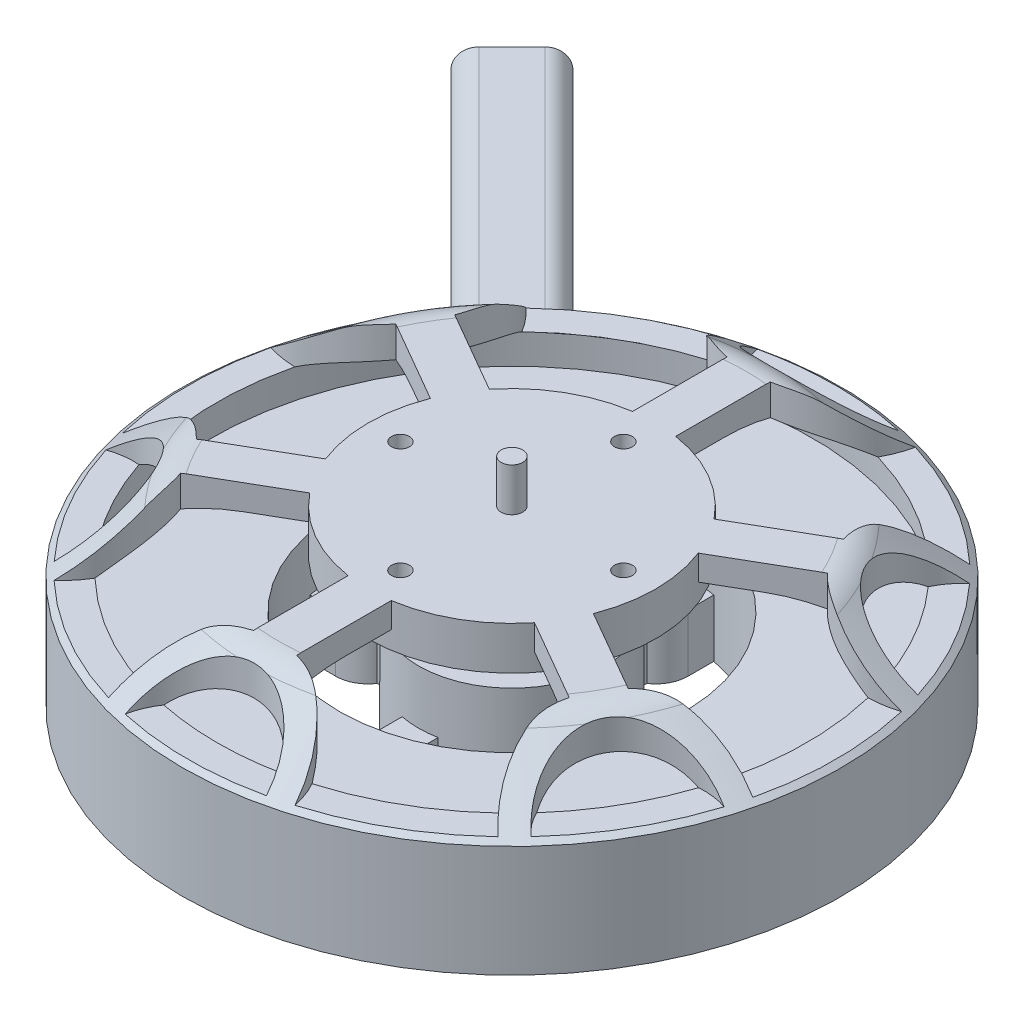
SolidWorks part; units mm, degrees
ref_plane "Front Plane" through (0, 0, 0) normal (0, 0, 1) x (1, 0, 0)
ref_plane "Top Plane" through (0, 0, 0) normal (0, 1, 0) x (1, 0, 0)
ref_plane "Right Plane" through (0, 0, 0) normal (1, 0, 0) x (0, 0, -1)
ref_axis "Axis1" through (0, 40.089, 0) along (0, -1, 0)
sketch "Sketch1" plane through (0, 0, 0) normal (0, 0, 1) x (1, 0, 0)
  line L0 (0, 0) -> (9.65, 0)
  line L1 (9.65, 0) -> (9.65, 3.93)
  line L2 (9.65, 3.93) -> (27.5, 3.93)
  line L3 (27.5, 3.93) -> (45.83, 8.08)
  line L4 (45.83, 8.08) -> (45.83, 23.58)
  line L5 (45.83, 23.58) -> (36.1322, 30.9557)
  line L6 (32.5, 32.18) -> (1.5, 32.18)
  line L7 (1.5, 32.18) -> (1.5, 38.18)
  line L8 (1.5, 38.18) -> (0, 38.18)
  line L9 (0, 38.18) -> (0, 0) construction
  line L10 (0, 0) -> (0, 38.18)
  arc A0 (36.1322, 30.9557) -> (32.5, 32.18) centre (32.5, 26.18) ccw
  dimension "D10" = 6
  dimension "D1" = 3
  dimension "D2" = 6
  dimension "D3" = 28.25
  dimension "D4" = 3.93
  dimension "D5" = 19.3
  dimension "D6" = 4.15
  dimension "D7" = 91.66
  dimension "D8" = 55
  dimension "D9" = 65
  dimension "D11" = 15.5
revolve "Revolve1" add sketch "Sketch1" angle 360 about L9
sketch "Sketch2" plane through (0, 3.93, 0) normal (0, -1, 0) x (1, 0, 0)
  line L0 (0, 0) -> (0, 27.5) construction
  line L1 (2.5, 12.7574) -> (2.5, 16.2583)
  line L2 (4.5, 20) -> (4.5, 23.5744)
  line L3 (0, 0) -> (16.9706, 16.9706) construction
  line L4 (20, 4.5) -> (23.5744, 4.5)
  line L5 (12.7574, 2.5) -> (16.2583, 2.5)
  line L6 (20, -4.5) -> (23.5744, -4.5)
  line L7 (4.5, -20) -> (4.5, -23.5744)
  line L8 (2.5, -12.7574) -> (2.5, -16.2583)
  line L9 (12.7574, -2.5) -> (16.2583, -2.5)
  line L10 (-4.5, -20) -> (-4.5, -23.5744)
  line L11 (-20, -4.5) -> (-23.5744, -4.5)
  line L12 (-12.7574, -2.5) -> (-16.2583, -2.5)
  line L13 (-2.5, -12.7574) -> (-2.5, -16.2583)
  line L14 (-20, 4.5) -> (-23.5744, 4.5)
  line L15 (-4.5, 20) -> (-4.5, 23.5744)
  line L16 (-2.5, 12.7574) -> (-2.5, 16.2583)
  line L17 (-12.7574, 2.5) -> (-16.2583, 2.5)
  arc A0 (4.5, 23.5744) -> (23.5744, 4.5) centre (0, 0) cw
  arc A1 (4.5, 20) -> (2.5, 16.2583) centre (0, 20) cw
  arc A2 (2.5, 12.7574) -> (12.7574, 2.5) centre (0, 0) cw
  circle A3 centre (0, 0) radius 27.5 construction
  arc A4 (20, 4.5) -> (16.2583, 2.5) centre (20, 0) ccw
  arc A5 (20, -4.5) -> (16.2583, -2.5) centre (20, 0) cw
  arc A6 (23.5744, -4.5) -> (4.5, -23.5744) centre (0, 0) cw
  arc A7 (4.5, -20) -> (2.5, -16.2583) centre (0, -20) ccw
  arc A8 (12.7574, -2.5) -> (2.5, -12.7574) centre (0, 0) cw
  arc A9 (-4.5, -20) -> (-2.5, -16.2583) centre (0, -20) cw
  arc A10 (-4.5, -23.5744) -> (-23.5744, -4.5) centre (0, 0) cw
  arc A11 (-20, -4.5) -> (-16.2583, -2.5) centre (-20, 0) ccw
  arc A12 (-2.5, -12.7574) -> (-12.7574, -2.5) centre (0, 0) cw
  arc A13 (-20, 4.5) -> (-16.2583, 2.5) centre (-20, 0) cw
  arc A14 (-23.5744, 4.5) -> (-4.5, 23.5744) centre (0, 0) cw
  arc A15 (-4.5, 20) -> (-2.5, 16.2583) centre (0, 20) ccw
  arc A16 (-12.7574, 2.5) -> (-2.5, 12.7574) centre (0, 0) cw
  point P4 (0, 20)
  point P51 (0, 0)
  dimension "D2" = 13
  dimension "D5" = 24
  dimension "D1" = 20
  dimension "D3" = 5
  dimension "D4" = 9
  dimension "D6" = 45
  dimension "D7" = 4
hole_wizard "M4x0.7 Tapped Hole1" positions "3DSketch1" profile "Sketch4" tap size "M4x0.7" standard "ANSI Metric"
sketch3d "3DSketch1"
  point P0 (-20, 3.93, 0)
  point P3 (0, 3.93, 20)
  point P6 (20, 3.93, 0)
  point P9 (0, 3.93, -20)
sketch "Sketch4" plane through (-20, 3.93, 0) normal (1, 0, 0) x (0, 0, -1)
  line L0 (0, 0) -> (0, 8.9914)
  line L1 (0, 8.9914) -> (1.65, 8)
  line L2 (1.65, 8) -> (1.65, 0)
  line L5 (1.65, 0) -> (0, 0)
  line L10 (0, 8.9914) -> (-1.65, 8) construction
  line L11 (0, -6.35) -> (0, 107.95) construction
  dimension "Tap Drill Dia." = 3.3
  dimension "Tap Drill Depth" = 8
  dimension "Drill Angle" = 118
cosmetic thread "Hole Thread1" parameters "D1"=7.874, "D2"=4
cosmetic thread "Hole Thread2" parameters "D1"=7.874, "D2"=4
cosmetic thread "Hole Thread3" parameters "D1"=7.874, "D2"=4
cosmetic thread "Hole Thread4" parameters "D1"=7.874, "D2"=4
extrude "Cut-Extrude1" cut sketch "Sketch2" against normal blind 8
sketch "Sketch5" plane through (0, 0, 0) normal (0, 0, 1) x (1, 0, 0)
  line L0 (24, 19.43) -> (41.83, 19.43)
  line L1 (-27.5, 3.93) -> (27.5, 3.93) construction
  line L2 (41.83, 19.43) -> (41.83, 23.58)
  line L3 (45.83, 8.08) -> (45.83, 23.58) construction
  line L4 (10, 19.43) -> (13, 19.43)
  line L5 (13, 19.43) -> (13, 11.93)
  line L6 (13, 11.93) -> (24, 11.93)
  line L7 (24, 11.93) -> (24, 19.43)
  line L8 (0, 40.089) -> (0, -1.909) construction
  line L9 (4.5, 11.93) -> (23.5744, 11.93) construction
  line L10 (45.83, 23.58) -> (-45.83, 23.58) construction
  line L11 (20, 28.68) -> (26.6996, 28.68)
  line L12 (32.5, 32.18) -> (-32.5, 32.18) construction
  line L13 (41.83, 23.58) -> (45.83, 20.5378) construction
  line L14 (45.83, 23.58) -> (36.1322, 30.9557) construction
  line L15 (20, 28.68) -> (20, 26.18)
  line L16 (20, 26.18) -> (10, 26.18)
  line L17 (10, 26.18) -> (10, 19.43)
  arc A0 (26.6996, 28.68) -> (41.83, 23.58) centre (26.6996, 3.6861) cw
  dimension "D1" = 15.5
  dimension "D2" = 4
  dimension "D3" = 13
  dimension "D4" = 24
  dimension "D5" = 3.5
  dimension "D6" = 20
  dimension "D7" = 6
  dimension "D8" = 10
revolve "Cut-Revolve3" cut sketch "Sketch5" angle 360 about axis through (0, 40.089, 0) along (0, -1, 0)
sketch "Sketch6" plane through (0, 0, 0) normal (0, 1, 0) x (1, 0, 0)
  line L0 (-3, 19.7737) -> (-3, 32.9241)
  line L1 (3, 19.7737) -> (3, 32.9241)
  line L2 (-3, 19.7737) -> (3, 19.7737) construction
  line L3 (0, 45.83) -> (0, 35.83) construction
  line L4 (15.6245, 12.4849) -> (27.0131, 19.0601)
  line L5 (18.6245, 7.2888) -> (30.0131, 13.864)
  line L6 (15.6245, 12.4849) -> (18.6245, 7.2888) construction
  line L7 (39.6899, 22.915) -> (31.0297, 17.915) construction
  line L8 (18.6245, -7.2888) -> (30.0131, -13.864)
  line L9 (15.6245, -12.4849) -> (27.0131, -19.0601)
  line L10 (18.6245, -7.2888) -> (15.6245, -12.4849) construction
  line L11 (39.6899, -22.915) -> (31.0297, -17.915) construction
  line L12 (3, -19.7737) -> (3, -32.9241)
  line L13 (-3, -19.7737) -> (-3, -32.9241)
  line L14 (3, -19.7737) -> (-3, -19.7737) construction
  line L15 (0, -45.83) -> (0, -35.83) construction
  line L16 (-15.6245, -12.4849) -> (-27.0131, -19.0601)
  line L17 (-18.6245, -7.2888) -> (-30.0131, -13.864)
  line L18 (-15.6245, -12.4849) -> (-18.6245, -7.2888) construction
  line L19 (-39.6899, -22.915) -> (-31.0297, -17.915) construction
  line L20 (-18.6245, 7.2888) -> (-30.0131, 13.864)
  line L21 (-15.6245, 12.4849) -> (-27.0131, 19.0601)
  line L22 (-18.6245, 7.2888) -> (-15.6245, 12.4849) construction
  line L23 (-39.6899, 22.915) -> (-31.0297, 17.915) construction
  line L24 (0, 15.5) -> (15.5, 0) construction
  line L25 (15.5, 0) -> (0, -15.5) construction
  line L26 (0, -15.5) -> (-15.5, 0) construction
  line L27 (-15.5, 0) -> (0, 15.5) construction
  arc A1 (-9.9403, 44.739) -> (9.9403, 44.739) centre (0, 45.83) ccw
  circle A2 centre (0, 0) radius 45.83 construction
  arc A3 (-13.1108, 43.9146) -> (-3, 32.9241) centre (0, 45.83) ccw
  arc A4 (13.1108, 43.9146) -> (3, 32.9241) centre (0, 45.83) cw
  arc A5 (-13.1108, 43.9146) -> (-9.9403, 44.739) centre (0, 0) cw
  arc A6 (9.9403, 44.739) -> (13.1108, 43.9146) centre (0, 0) cw
  arc A7 (33.775, 30.9781) -> (43.7153, 13.7609) centre (39.6899, 22.915) ccw
  arc A8 (31.4758, 33.3116) -> (27.0131, 19.0601) centre (39.6899, 22.915) ccw
  arc A9 (44.5866, 10.603) -> (30.0131, 13.864) centre (39.6899, 22.915) cw
  arc A10 (31.4758, 33.3116) -> (33.775, 30.9781) centre (0, 0) cw
  arc A11 (43.7153, 13.7609) -> (44.5866, 10.603) centre (0, 0) cw
  arc A12 (43.7153, -13.7609) -> (33.775, -30.9781) centre (39.6899, -22.915) ccw
  arc A13 (44.5866, -10.603) -> (30.0131, -13.864) centre (39.6899, -22.915) ccw
  arc A14 (31.4758, -33.3116) -> (27.0131, -19.0601) centre (39.6899, -22.915) cw
  arc A15 (44.5866, -10.603) -> (43.7153, -13.7609) centre (0, 0) cw
  arc A16 (33.775, -30.9781) -> (31.4758, -33.3116) centre (0, 0) cw
  arc A17 (9.9403, -44.739) -> (-9.9403, -44.739) centre (0, -45.83) ccw
  arc A18 (13.1108, -43.9146) -> (3, -32.9241) centre (0, -45.83) ccw
  arc A19 (-13.1108, -43.9146) -> (-3, -32.9241) centre (0, -45.83) cw
  arc A20 (13.1108, -43.9146) -> (9.9403, -44.739) centre (0, 0) cw
  arc A21 (-9.9403, -44.739) -> (-13.1108, -43.9146) centre (0, 0) cw
  arc A22 (-33.775, -30.9781) -> (-43.7153, -13.7609) centre (-39.6899, -22.915) ccw
  arc A23 (-31.4758, -33.3116) -> (-27.0131, -19.0601) centre (-39.6899, -22.915) ccw
  arc A24 (-44.5866, -10.603) -> (-30.0131, -13.864) centre (-39.6899, -22.915) cw
  arc A25 (-31.4758, -33.3116) -> (-33.775, -30.9781) centre (0, 0) cw
  arc A26 (-43.7153, -13.7609) -> (-44.5866, -10.603) centre (0, 0) cw
  arc A27 (-43.7153, 13.7609) -> (-33.775, 30.9781) centre (-39.6899, 22.915) ccw
  arc A28 (-44.5866, 10.603) -> (-30.0131, 13.864) centre (-39.6899, 22.915) ccw
  arc A29 (-31.4758, 33.3116) -> (-27.0131, 19.0601) centre (-39.6899, 22.915) cw
  arc A30 (-44.5866, 10.603) -> (-43.7153, 13.7609) centre (0, 0) cw
  arc A31 (-33.775, 30.9781) -> (-31.4758, 33.3116) centre (0, 0) cw
  arc A32 (3, 19.7737) -> (15.6245, 12.4849) centre (0, 0) cw
  arc A33 (18.6245, 7.2888) -> (18.6245, -7.2888) centre (0, 0) cw
  arc A34 (15.6245, -12.4849) -> (3, -19.7737) centre (0, 0) cw
  arc A35 (-3, -19.7737) -> (-15.6245, -12.4849) centre (0, 0) cw
  arc A36 (-18.6245, -7.2888) -> (-18.6245, 7.2888) centre (0, 0) cw
  arc A37 (-3, 19.7737) -> (-15.6245, 12.4849) centre (0, 0) ccw
  point P0 (0, 19.7737)
  point P17 (0, 15.5)
  point P28 (15.5, 0)
  point P38 (0, -15.5)
  point P68 (0, 0)
  point P69 (-15.5, 0)
  dimension "D1" = 6
  dimension "D3" = 3.25
  dimension "D5" = 20
  dimension "D2" = 6
  dimension "D4" = 10
  dimension "D6" = 15.5
extrude "Cut-Extrude3" cut sketch "Sketch6" against normal blind 8 from surface flip side to cut starting at face at (0, 32.18, 1.5)
hole_wizard "M3x0.5 Tapped Hole1" positions "Sketch8" profile "Sketch10" tap size "M3x0.5" standard "ANSI Metric" end condition up to next
sketch "Sketch8" plane through (0, 32.18, 0) normal (0, 1, 0) x (1, 0, 0)
  point P0 (0, 15.5)
  point P3 (15.5, 0)
  point P6 (0, -15.5)
  point P9 (-15.5, 0)
sketch "Sketch10" plane through (0, 32.18, -15.5) normal (1, 0, 0) x (0, 0, 1)
  line L0 (0, 0) -> (0, 6)
  line L1 (0, 6) -> (1.25, 6)
  line L2 (1.25, 6) -> (1.25, 0)
  line L5 (1.25, 0) -> (0, 0)
  line L11 (0, -6.35) -> (0, 107.95) construction
  dimension "Thru Tap Drill Dia." = 2.5
  dimension "Thru Tap Drill Depth" = 6
cosmetic thread "Hole Thread5" parameters "D2"=3
cosmetic thread "Hole Thread6" parameters "D2"=3
cosmetic thread "Hole Thread7" parameters "D2"=3
cosmetic thread "Hole Thread8" parameters "D2"=3
sketch "Sketch11" plane through (0, 0, 0) normal (0, 1, 0) x (1, 0, 0)
  line L0 (-26.0427, 21.4465) -> (-21.4465, 26.0427) construction
  line L1 (-27.9873, 23.3911) -> (-23.3911, 27.9873)
  line L2 (-24.0982, 19.502) -> (-19.502, 24.0982)
  line L3 (-23.7446, 23.7446) -> (0, 0) construction
  line L4 (-20, 0) -> (0, 20) construction
  line L5 (-27.9873, 19.502) -> (-19.502, 27.9873) construction
  line L6 (-25.6892, 25.6892) -> (-32.4067, 32.4067) construction
  arc A0 (-27.9873, 23.3911) -> (-24.0982, 19.502) centre (-26.0427, 21.4465) ccw
  arc A1 (-19.502, 24.0982) -> (-23.3911, 27.9873) centre (-21.4465, 26.0427) ccw
  arc A2 (3, 19.7737) -> (-3, 19.7737) centre (0, 0) ccw construction
  circle A3 centre (0, 0) radius 45.83 construction
  point P2 (-23.7446, 23.7446)
  dimension "D1" = 12
  dimension "D2" = 5.5
  dimension "D3" = 9.5
extrude "Boss-Extrude1" add sketch "Sketch11" against normal blind 19.05 from offset 12.7
ref_plane "Plane1" through (0, 0, 0) normal (-0.7071, 0, 0.7071) x (0.7071, 0, 0.7071)
sketch "Sketch12" plane through (0, 0, 0) normal (-0.7071, 0, 0.7071) x (0.7071, 0, 0.7071)
  line L0 (-36.33, -6.35) -> (-36.33, 5.962) construction
  line L1 (-49.03, -19.05) -> (-150.63, -19.05)
  arc A0 (-36.33, -6.35) -> (-49.03, -19.05) centre (-49.03, -6.35) cw
  dimension "D1" = 12.7
  dimension "D2" = 101.6
sketch "Sketch13" plane through (0, -6.35, 0) normal (0, -1, 0) x (1, 0, 0)
  line L2 (-27.9873, -23.3911) -> (-23.3911, -27.9873)
  line L3 (-19.502, -24.0982) -> (-24.0982, -19.502)
  line L4 (-27.9873, -23.3911) -> (-23.3911, -27.9873)
  line L5 (-19.502, -24.0982) -> (-24.0982, -19.502)
  arc A2 (-24.0982, -19.502) -> (-27.9873, -23.3911) centre (-26.0427, -21.4465) ccw
  arc A3 (-23.3911, -27.9873) -> (-19.502, -24.0982) centre (-21.4465, -26.0427) ccw
  arc A4 (-24.0982, -19.502) -> (-27.9873, -23.3911) centre (-26.0427, -21.4465) ccw
  arc A5 (-23.3911, -27.9873) -> (-19.502, -24.0982) centre (-21.4465, -26.0427) ccw
  dimension "D1" = 0
sweep "Sweep1" add profiles "Sketch13" path "Sketch12"
equation "\"INTERIOR_STATOR_BORE_OD\"= 48MM"
equation "\"INTERIOR_STATOR_BORE_ID\"= 26mm"
equation "\"D5@Sketch2\"=\"INTERIOR_STATOR_BORE_OD\"/2"
equation "\"D2@Sketch2\"=\"INTERIOR_STATOR_BORE_ID\"/2"
equation "\"D3@Sketch5\"=\"INTERIOR_STATOR_BORE_ID\"/2"
equation "\"D4@Sketch5\"=\"INTERIOR_STATOR_BORE_OD\"/2"
